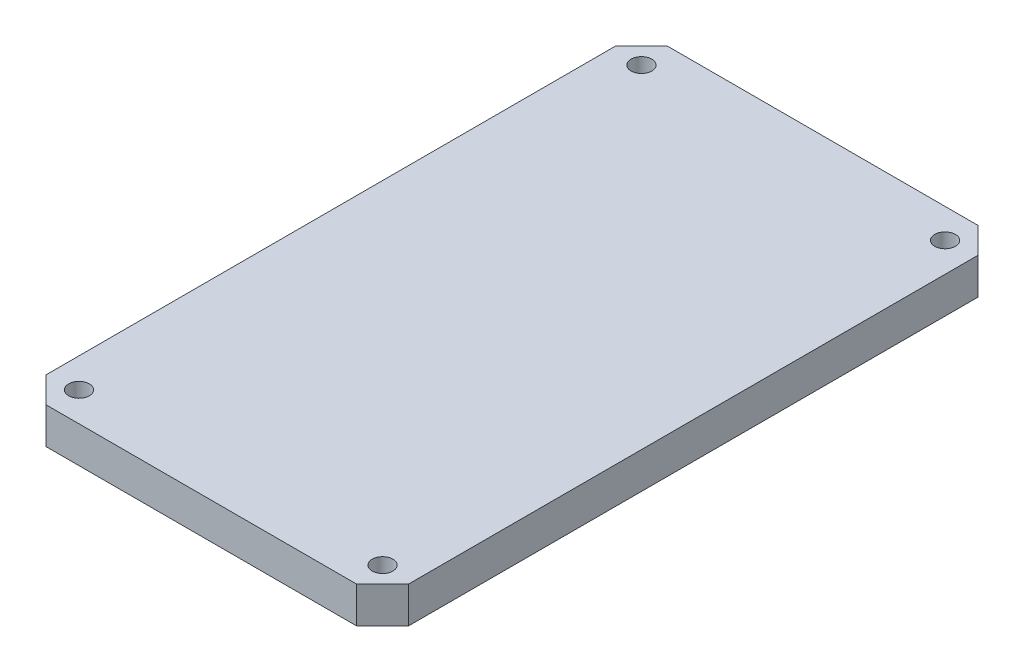
SolidWorks part; units mm, degrees
note: The reader was unsure of these and kept them because the rebuilt part matched: shared geometry of "Sketch2<3>", "Sketch2<4>".
ref_plane "Front Plane" through (0, 0, 0) normal (0, 0, 1) x (1, 0, 0)
ref_plane "Top Plane" through (0, 0, 0) normal (0, 1, 0) x (1, 0, 0)
ref_plane "Right Plane" through (0, 0, 0) normal (1, 0, 0) x (0, 0, -1)
sketch "Sketch2" plane through (0, 0, 0) normal (0, 1, 0) x (1, 0, 0)
  line L0 (-44.45, 69.85) -> (-38.1, 76.2)
  line L1 (-38.1, 76.2) -> (38.1, 76.2)
  line L2 (-44.45, 69.85) -> (-44.45, -69.85)
  line L3 (-38.1, -76.2) -> (38.1, -76.2)
  line L4 (44.45, 69.85) -> (44.45, -69.85)
  line L5 (-44.45, 76.2) -> (44.45, -76.2) construction
  line L6 (-44.45, -76.2) -> (44.45, 76.2) construction
  line L7 (38.1, 76.2) -> (44.45, 69.85)
  line L8 (-44.45, -69.85) -> (-38.1, -76.2)
  line L9 (38.1, -76.2) -> (44.45, -69.85)
  line L10 (-41.275, 68.5349) -> (-41.275, -68.5349)
  line L11 (-41.275, -68.5349) -> (-36.7849, -73.025)
  line L12 (-36.7849, -73.025) -> (36.7849, -73.025)
  line L13 (36.7849, -73.025) -> (41.275, -68.5349)
  line L14 (41.275, 68.5349) -> (41.275, -68.5349)
  line L15 (36.7849, 73.025) -> (41.275, 68.5349)
  line L16 (-36.7849, 73.025) -> (36.7849, 73.025)
  line L17 (-41.275, 68.5349) -> (-36.7849, 73.025)
  line L18 (-37.2339, 68.9839) -> (-39.0299, 70.7799) construction
  line L19 (0, 0) -> (41.275, 0) construction
  line L20 (0, 0) -> (0, -73.025) construction
  line L21 (37.2339, 68.9839) -> (39.0299, 70.7799) construction
  line L22 (37.2339, -68.9839) -> (39.0299, -70.7799) construction
  line L23 (-37.2339, -68.9839) -> (-39.0299, -70.7799) construction
  line L24 (-40.64, 68.2718) -> (-40.64, -68.2718) construction
  line L25 (-40.64, -68.2718) -> (-36.5218, -72.39) construction
  line L26 (-36.5218, -72.39) -> (36.5218, -72.39) construction
  line L27 (36.5218, -72.39) -> (40.64, -68.2718) construction
  line L28 (40.64, 68.2718) -> (40.64, -68.2718) construction
  line L29 (36.5218, 72.39) -> (40.64, 68.2718) construction
  line L30 (-36.5218, 72.39) -> (36.5218, 72.39) construction
  line L31 (-40.64, 68.2718) -> (-36.5218, 72.39) construction
  line L32 (-40.64, 63.4081) -> (-40.64, -63.4081)
  line L33 (-31.6581, -72.39) -> (31.6581, -72.39)
  line L34 (40.64, -63.4081) -> (40.64, 63.4081)
  line L35 (31.6581, 72.39) -> (-31.6581, 72.39)
  circle A0 centre (-37.2339, 68.9839) radius 2.54
  circle A1 centre (-37.2339, 68.9839) radius 4.066 construction
  circle A2 centre (37.2339, 68.9839) radius 4.066 construction
  circle A3 centre (37.2339, 68.9839) radius 2.54
  circle A4 centre (-37.2339, 68.9839) radius 4.701 construction
  circle A5 centre (37.2339, 68.9839) radius 4.701 construction
  circle A6 centre (37.2339, -68.9839) radius 4.701 construction
  circle A7 centre (37.2339, -68.9839) radius 4.066 construction
  circle A8 centre (37.2339, -68.9839) radius 2.54
  circle A9 centre (-37.2339, -68.9839) radius 4.701 construction
  circle A10 centre (-37.2339, -68.9839) radius 4.066 construction
  circle A11 centre (-37.2339, -68.9839) radius 2.54
  arc A12 (32.844, 70.6657) -> (38.9157, 64.594) centre (37.2339, 68.9839) ccw
  arc A13 (-38.9157, 64.594) -> (-32.844, 70.6657) centre (-37.2339, 68.9839) ccw
  arc A14 (-38.9157, -64.594) -> (-32.844, -70.6657) centre (-37.2339, -68.9839) cw
  arc A15 (32.844, -70.6657) -> (38.9157, -64.594) centre (37.2339, -68.9839) cw
  arc A16 (-31.6581, -72.39) -> (-32.844, -70.6657) centre (-31.6581, -71.12) cw
  arc A17 (-40.64, -63.4081) -> (-38.9157, -64.594) centre (-39.37, -63.4081) ccw
  arc A18 (40.64, -63.4081) -> (38.9157, -64.594) centre (39.37, -63.4081) cw
  arc A19 (31.6581, -72.39) -> (32.844, -70.6657) centre (31.6581, -71.12) ccw
  arc A20 (40.64, 63.4081) -> (38.9157, 64.594) centre (39.37, 63.4081) ccw
  arc A21 (31.6581, 72.39) -> (32.844, 70.6657) centre (31.6581, 71.12) cw
  arc A22 (-31.6581, 72.39) -> (-32.844, 70.6657) centre (-31.6581, 71.12) ccw
  arc A23 (-40.64, 63.4081) -> (-38.9157, 64.594) centre (-39.37, 63.4081) cw
  point P0 (0, 0)
  point P70 (-33.9939, -72.39)
  point P73 (-40.64, -65.7439)
  point P76 (40.64, -65.7439)
  point P79 (33.9939, -72.39)
  point P82 (40.64, 65.7439)
  point P85 (33.9939, 72.39)
  point P88 (-33.9939, 72.39)
  point P91 (-40.64, 65.7439)
  dimension "D4" = 5.08
  dimension "D8" = 1.27
  dimension "D1" = 152.4
  dimension "D2" = 88.9
  dimension "D5" = 2.54
  dimension "D3" = 3.175
  dimension "D6" = 0.635
  dimension "D7" = 0.635
extrude "Boss-Extrude1" add sketch "Sketch2" along normal blind 2.54 contours L3 L9 L4 L7 L1 L0 L2 L8 L10 L17 L16 L15 L14 L13 L12 L11 | L11 A11 L12 L13 A8 L14 L15 A3 L16 L17 A0 L10 L32 A23 A13 A22 L35 A21 A12 A20 L34 A18 A15 A19 L33 A16 A14 A17 | A23 L32 A17 A14 A16 L33 A19 A15 A18 L34 A20 A12 A21 L35 A22 A13
extrude "Boss-Extrude2" add sketch "Sketch2<3>" against normal blind 6.35 contours L3 L9 L4 L7 L1 L0 L2 L8 L10 L17 L16 L15 L14 L13 L12 L11 | L11 A11 L12 L13 A8 L14 L15 A3 L16 L17 A0 L10 L32 A23 A13 A22 L35 A21 A12 A20 L34 A18 A15 A19 L33 A16 A14 A17
sketch "Sketch2<3>" plane through (0, 0, 0) normal (0, 1, 0) x (1, 0, 0) same geometry as "Sketch2"
extrude "Boss-Extrude3" add sketch "Sketch2<4>" against normal blind 1.6 from offset 2.54 separate body contours A23 L32 A17 A14 A16 L33 A19 A15 A18 L34 A20 A12 A21 L35 A22 A13
sketch "Sketch2<4>" plane through (0, 0, 0) normal (0, 1, 0) x (1, 0, 0) same geometry as "Sketch2"
